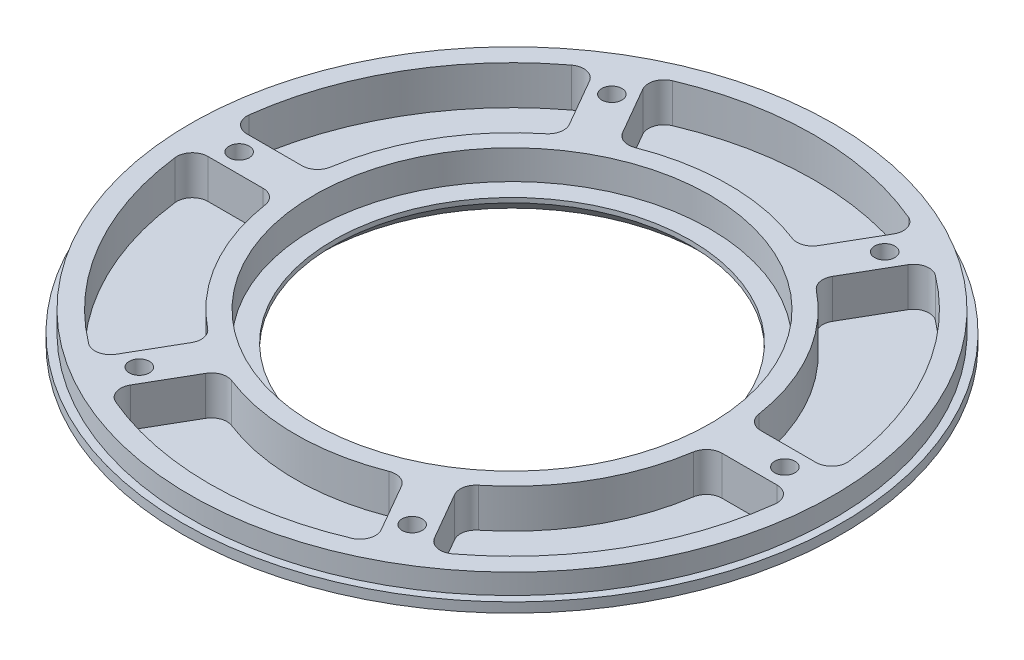
SolidWorks part; units mm, degrees
material "6061-T6 (SS)"
ref_plane "Front Plane" through (0, 0, 0) normal (0, 0, 1) x (1, 0, 0)
ref_plane "Top Plane" through (0, 0, 0) normal (0, 1, 0) x (1, 0, 0)
ref_plane "Right Plane" through (0, 0, 0) normal (1, 0, 0) x (0, 0, -1)
sketch "Sketch2" plane through (0, 0, 0) normal (1, 0, 0) x (0, 0, -1)
  line L0 (-45.8, 0) -> (-82.55, 0)
  line L1 (-82.55, 0) -> (-82.55, 12.7)
  line L2 (-82.55, 12.7) -> (-50.8, 12.7)
  line L3 (-45.8, 0) -> (-45.8, 5.2)
  line L4 (-45.8, 5.2) -> (-50.8, 5.2)
  line L5 (-50.8, 5.2) -> (-50.8, 12.7)
  line L6 (-80.2166, 12.7) -> (-80.2166, 0) construction
  dimension "D1" = 82.55
  dimension "D2" = 12.7
  dimension "D3" = 50.8
  dimension "D4" = 5
  dimension "D5" = 7.5
ref_axis "Axis1" through (0, -0.5, 0) along (0, 1, 0)
revolve "Revolve1" add sketch "Sketch2" angle 360 about axis through (0, -0.5, 0) along (0, 1, 0)
hole_wizard "#6 (0.204) Diameter Hole1" positions "Sketch6" profile "Sketch7" hole size "#6" standard "ANSI Inch" end condition through all
sketch "Sketch6" plane through (0, 12.7, 0) normal (0, 1, 0) x (1, 0, 0)
  line L0 (0, 0) -> (-69.8201, 120.932) construction
  line L2 (0, 0) -> (0, 109.0908) construction
  point P0 (-35, 60.6218)
  dimension "D1" = 30
  dimension "D2" = 70
sketch "Sketch7" plane through (-35, 12.7, -60.6218) normal (1, 0, 0) x (0, 0, 1)
  line L0 (0, 0) -> (0, 12.7)
  line L1 (0, 12.7) -> (2.5908, 12.7)
  line L2 (2.5908, 12.7) -> (2.5908, 0)
  line L5 (2.5908, 0) -> (0, 0)
  line L11 (0, -6.35) -> (0, 107.95) construction
  dimension "Thru Hole Dia." = 5.1816
  dimension "Thru Hole Depth" = 12.7
pattern_circular "CirPattern3" count 6 over 360 about axis through (0, -0.5, 0) along (0, 1, 0) of "#6 (0.204) Diameter Hole1"
sketch "Sketch8" plane through (0, 12.7, 0) normal (0, 1, 0) x (1, 0, 0)
  line L4 (0, 0) -> (0, 93.9995) construction
  line L5 (-23.3321, 50.4124) -> (-34.3642, 69.5205)
  line L6 (23.3321, 50.4124) -> (34.3642, 69.5205)
  line L7 (0, 0) -> (-35, 60.6218) construction
  arc A0 (-23.3321, 50.4124) -> (23.3321, 50.4124) centre (0, 0) cw
  arc A1 (-34.3642, 69.5205) -> (34.3642, 69.5205) centre (0, 0) cw
  circle A2 centre (0, 0) radius 82.55 construction
  dimension "D1" = 27
  dimension "D2" = 5
  dimension "D3" = 5
extrude "Cut-Extrude1" cut sketch "Sketch8" against normal blind 10
fillet "Fillet1" radius 4 4 edges at (-23.3321, 7.7, -50.4124) (23.3321, 7.7, -50.4124) (34.3642, 7.7, -69.5205) (-34.3642, 7.7, -69.5205)
pattern_circular "CirPattern4" count 6 over 360 about axis through (0, -0.5, 0) along (0, 1, 0) of "Cut-Extrude1", "Fillet1"
chamfer "Chamfer1" distance 4 angle 45 1 edges at (0, 0, -45.8)
sketch "Sketch10" plane through (0, 0, 0) normal (0, -1, 0) x (1, 0, 0)
  circle A0 centre (0, 0) radius 82.55
  circle A1 centre (0, 0) radius 84.55
  circle A2 centre (0, 0) radius 82.55 construction
  dimension "D1" = 2
extrude "Boss-Extrude1" add sketch "Sketch10" against normal blind 7.5
chamfer "Chamfer3" distance 5 angle 60 1 edges at (0, 0, -84.55) first distance on face at (0, 7.5, -84.55)
fillet "Fillet4" radius 5 1 edges at (0, 0, 75.8897)
equation "\"TubeDiameter\" = 6.500in"
